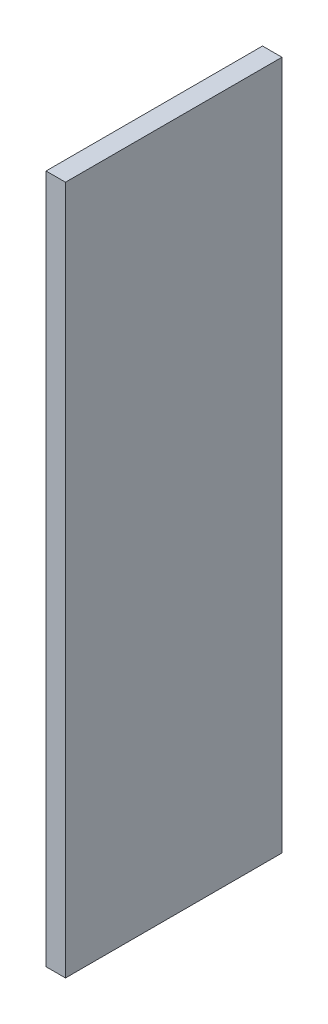
SolidWorks part; units mm, degrees
ref_plane "Front Plane" through (0, 0, 0) normal (0, 0, 1) x (1, 0, 0)
ref_plane "Top Plane" through (0, 0, 0) normal (0, 1, 0) x (1, 0, 0)
ref_plane "Right Plane" through (0, 0, 0) normal (1, 0, 0) x (0, 0, -1)
sketch "Sketch1" plane through (0, 0, 0) normal (1, 0, 0) x (0, 0, -1)
  line L1 (-30.4666, 598.9576) -> (172.7334, 598.9576)
  line L2 (-30.4666, 598.9576) -> (-30.4666, -47.9804)
  line L3 (-30.4666, -47.9804) -> (172.7334, -47.9804)
  line L4 (172.7334, 598.9576) -> (172.7334, -47.9804)
extrude "Boss-Extrude1" add sketch "Sketch1" along normal blind 18.2562 contours L2 L1 L4 L3
